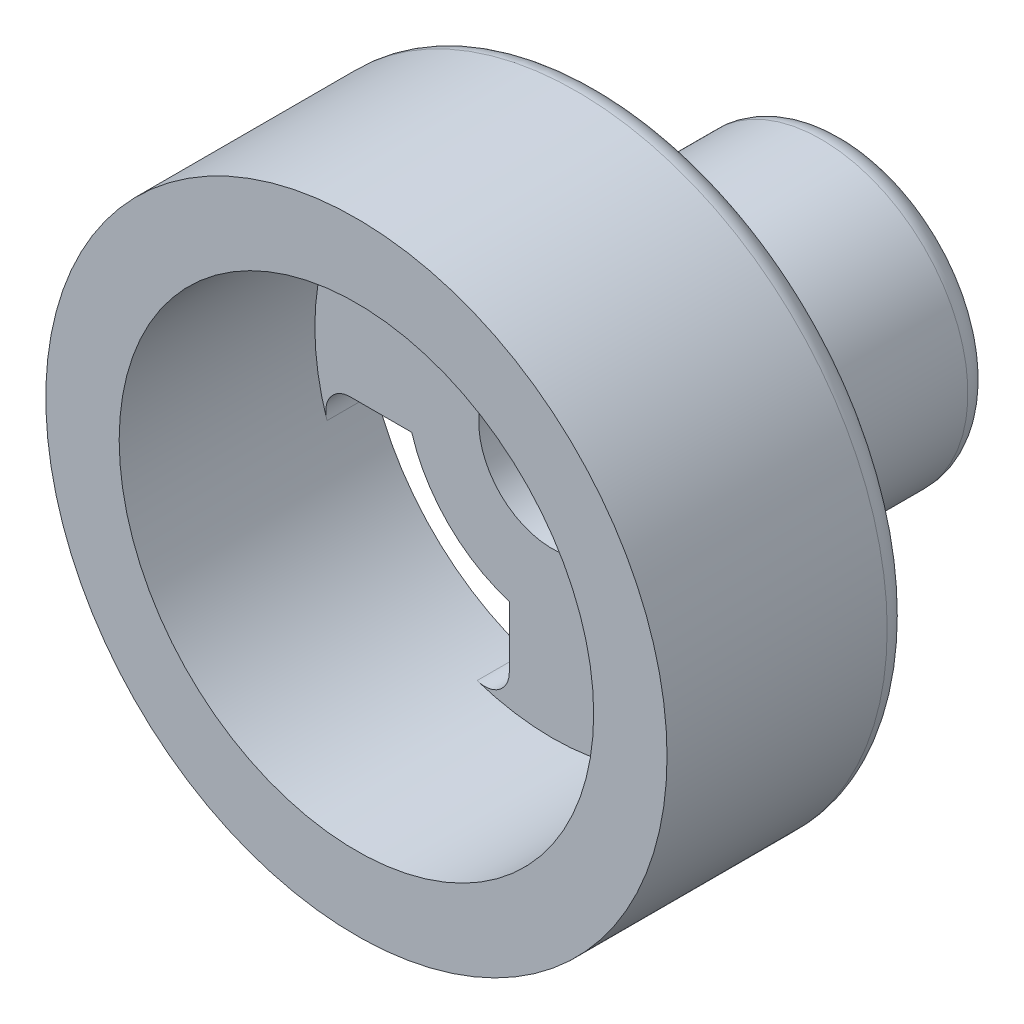
SolidWorks part; units mm, degrees
ref_plane "Plano frontal" through (0, 0, 0) normal (0, 0, 1) x (1, 0, 0)
ref_plane "Plano superior" through (0, 0, 0) normal (0, 1, 0) x (1, 0, 0)
ref_plane "Plano direito" through (0, 0, 0) normal (1, 0, 0) x (0, 0, -1)
sketch "Esboço1" plane through (0, 0, 0) normal (0, 0, 1) x (1, 0, 0)
  circle A0 centre (0, 0) radius 9.7
  circle A1 centre (0, 0) radius 3
  circle A2 centre (0, 0) radius 12.7
  dimension "D1" = 19.4
  dimension "D2" = 6
  dimension "D3" = 3
extrude "Ressalto-extrusão1" add sketch "Esboço1" against normal blind 10 contours A2 A0 | A0 A1 region at (-9.4256, 0, 0) region at (-12.3408, 0, 0)
extrude "Corte-extrusão1" cut sketch "Esboço1<3>" against normal blind 8 contours A0 A1 region at (-9.4256, 0, 0)
sketch "Esboço1<3>" plane through (0, 0, 0) normal (0, 0, 1) x (1, 0, 0) same geometry as "Esboço1"
sketch "Esboço2" plane through (0, 0, -10) normal (0, 0, -1) x (-1, 0, 0)
  line L9 (9.5408, -1.75) -> (5.7391, -1.75)
  line L22 (1.75, 9.5408) -> (1.75, 5.7391)
  line L35 (-1.75, 9.5408) -> (-1.75, 5.7391)
  line L36 (-1.0361, -5.9099) -> (-1.6751, -9.5543) construction
  line L37 (1.6751, -9.5543) -> (1.0361, -5.9099) construction
  line L39 (9.5408, 1.75) -> (5.7391, 1.75)
  line L41 (-1.75, -9.5408) -> (-1.75, -5.7391)
  line L43 (1.75, -9.5408) -> (1.75, -5.7391)
  line L45 (-9.5408, 1.75) -> (-5.7391, 1.75)
  line L47 (-9.5408, -1.75) -> (-5.7391, -1.75)
  line L53 (1.75, -5.7391) -> (1.75, -9.5408)
  line L54 (1.75, 5.7391) -> (1.75, 9.5408)
  line L56 (5.7391, 1.75) -> (9.5408, 1.75)
  line L57 (-1.75, -5.7391) -> (-1.75, -9.5408)
  line L58 (-1.75, 5.7391) -> (-1.75, 9.5408)
  line L60 (-5.7391, 1.75) -> (-9.5408, 1.75)
  line L61 (-5.7391, -1.75) -> (-9.5408, -1.75)
  line L64 (5.7391, -1.75) -> (9.5408, -1.75)
  circle A0 centre (0, 0) radius 3 construction
  circle A1 centre (0, 0) radius 3
  circle A2 centre (0, 0) radius 6
  arc A4 (1.6751, -9.5543) -> (9.5408, -1.75) centre (0, 0) ccw
  circle A5 centre (0, 0) radius 9.7
  arc A6 (-1.6751, 9.5543) -> (-9.5408, 1.75) centre (0, 0) ccw
  arc A7 (9.5408, 1.75) -> (1.6751, 9.5543) centre (0, 0) ccw
  arc A8 (-9.5408, -1.75) -> (-1.6751, -9.5543) centre (0, 0) ccw
  point P27 (0, 0)
  point P33 (0, 0)
  point P43 (0, 0)
  point P57 (0, 0)
  circle M17 centre (0, 0) radius 3
  dimension "D2" = 3
  dimension "D3" = 3.5
  dimension "D1" = 3
  dimension "D4" = 4
extrude "Corte-extrusão3" cut sketch "Esboço2" against normal up to surface (2 mm away) contours L47 A8 L41 A2 | L35 A6 L45 A2 | L39 A7 L22 A2 | L43 A4 L9 A2 region at (-5.3952, -5.3952, -10) region at (-5.3952, 5.3952, -10) region at (5.3952, -5.3952, -10) region at (5.3952, 5.3952, -10) up to face at (3, 0, -8)
fillet "Filete1" radius 1 8 edges at (1.75, -9.5408, -9) (-1.75, -9.5408, -9) (9.5408, 1.75, -9) (9.5408, -1.75, -9) (-9.5408, -1.75, -9) (-9.5408, 1.75, -9) (-1.75, 9.5408, -9) (1.75, 9.5408, -9)
extrude "Ressalto-extrusão2" add sketch "Esboço2<5>" along normal blind 10 contours A2 M17 region at (-4.1226, -4.1226, -10)
sketch "Esboço2<5>" plane through (0, 0, -10) normal (0, 0, -1) x (-1, 0, 0) same geometry as "Esboço2"
fillet "Filete2" radius 1 4 edges at (6, 0, -10) (0, 6, -10) (-6, 0, -10) (0, -6, -10)
fillet "Filete3" radius 1 1 edges at (-6, 0, -20)
fillet "Filete4" radius 1 1 edges at (12.7, 0, -10)
